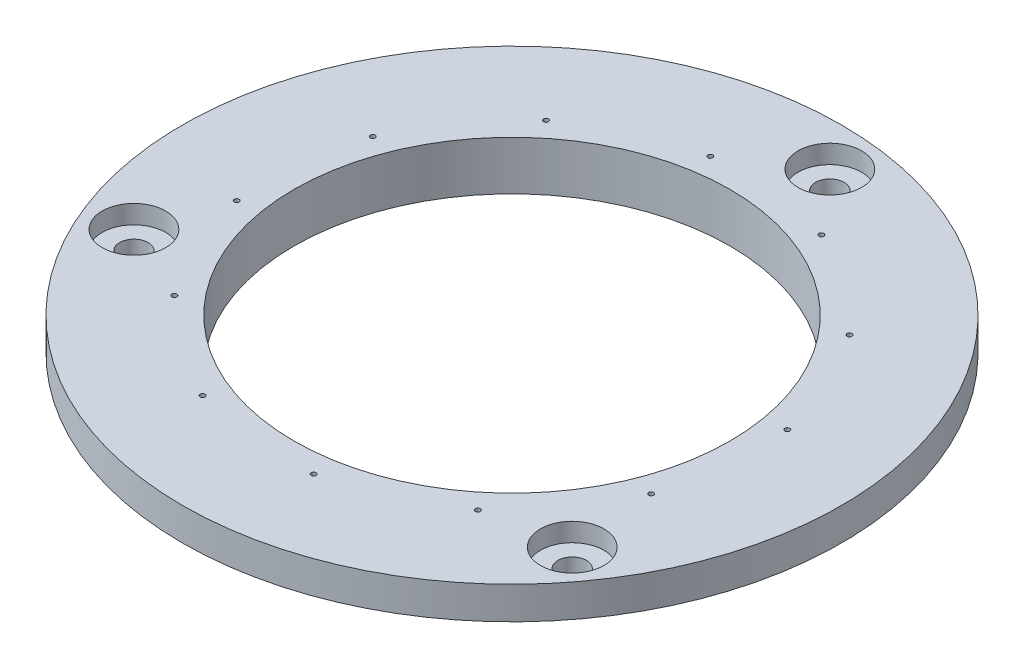
SolidWorks part; units mm, degrees
ref_plane "Front Plane" through (0, 0, 0) normal (0, 0, 1) x (1, 0, 0)
ref_plane "Top Plane" through (0, 0, 0) normal (0, 1, 0) x (1, 0, 0)
ref_plane "Right Plane" through (0, 0, 0) normal (1, 0, 0) x (0, 0, -1)
sketch "Sketch2" plane through (0, 0, 0) normal (0, 1, 0) x (1, 0, 0)
  circle A0 centre (0, 0) radius 63.5
  circle A1 centre (0, 0) radius 42
  dimension "D1" = 127
  dimension "D2" = 84
extrude "Boss-Extrude1" add sketch "Sketch2" along normal blind 9.45
sketch "Sketch15" plane through (0, 9.45, 0) normal (0, 1, 0) x (1, 0, 0)
  line L1 (6.244, 55) -> (-50.7534, -22.0925)
  line L2 (-50.7534, -22.0925) -> (44.5094, -32.9075)
  line L3 (44.5094, -32.9075) -> (6.244, 55)
  circle A0 centre (0, 0) radius 27.6766 construction
  point P1 (0, 53.3963)
  point P7 (0, 55.2781)
  point P8 (0, 56.4543)
  point P9 (0, 0)
  point P10 (0, 0)
  point P11 (0, 0)
  point P12 (0, 0)
  point P13 (0, 0)
  point P14 (0, 0)
  point P15 (0, 0)
  point P16 (0, 0)
  point P17 (0, 0)
  point P18 (0, 0)
  point P19 (0, 0)
  point P20 (0, 0)
hole_wizard "CBORE for M5 Hex Head Bolt1" positions "3DSketch8" profile "Sketch16" counterbore size "M5" standard "ANSI Metric"
sketch3d "3DSketch8"
  point P0 (6.244, 9.45, -55)
  point P3 (44.5094, 9.45, 32.9075)
  point P6 (-50.7534, 9.45, 22.0925)
sketch "Sketch16" plane through (6.244, 9.45, -55) normal (1, 0, 0) x (0, 0, 1)
  line L0 (0, 0) -> (0, 21.4024)
  line L1 (0, 21.4024) -> (2.75, 19.75)
  line L2 (2.75, 19.75) -> (2.75, 3.58)
  line L3 (2.75, 3.58) -> (6.12, 3.58)
  line L4 (6.12, 3.58) -> (6.12, 0)
  line L5 (6.12, 0) -> (0, 0)
  line L10 (0, 21.4024) -> (-2.75, 19.75) construction
  line L11 (0, -6.35) -> (0, 107.95) construction
  dimension "Hole Dia." = 5.5
  dimension "Hole Depth" = 19.75
  dimension "C'Bore Dia." = 12.24
  dimension "C'Bore Depth" = 3.58
  dimension "Drill Angle" = 118
sketch "Sketch26" plane through (0, 0, 0) normal (0, 1, 0) x (1, 0, 0)
  circle A0 centre (0, 0) radius 63.5
  dimension "D1" = 127
ref_axis "Axis1" through (0, 9.45, 0) along (0, -1, 0)
sketch "Sketch27" plane through (0, 0, 0) normal (0, 0, 1) x (1, 0, 0)
  line L0 (63.5, 0) -> (-63.5, 0) construction
  line L1 (63.5, 0) -> (58.5912, 0)
  line L2 (63.5, 0) -> (63.5, 3.175)
  line L3 (63.5, 3.175) -> (58.5912, 3.175)
  line L4 (58.5912, 0) -> (58.5912, 3.175)
  line L5 (69.85, 0) -> (-69.85, 0) construction
  line L6 (63.5, 0) -> (63.5, 9.45) construction
  line L7 (63.5, 0) -> (63.5, 9.45)
  line L8 (0, 9.45) -> (0, 0) construction
  line L9 (0, 0) -> (0, 15.4643) construction
  dimension "D1" = 117.1823
  dimension "D2" = 3.175
revolve "Cut-Revolve1" cut sketch "Sketch27" angle 360 about L9 region at (61.0456, 1.5875, 0)
hole_wizard "M1.2x0.25 Tapped Hole1" positions "Sketch28" profile "Sketch29" tap size "M1.2x0.25" standard "ANSI Metric" end condition through all
sketch "Sketch28" plane through (-17.102, 9.45, -64.2994) normal (0, 1, 0) x (0.108, 0, -0.9941)
  point P0 (-95.0061, 8.4911)
  point P3 (-74.3741, 20.6104)
  point P6 (-50.4466, 20.79)
  point P9 (-29.6349, 8.9817)
  point P12 (-17.5156, -11.6503)
  point P15 (-17.3361, -35.5778)
  point P18 (-29.1443, -56.3895)
  point P21 (-49.7764, -68.5087)
  point P24 (-73.7039, -68.6883)
  point P27 (-94.5155, -56.8801)
  point P30 (-106.6348, -36.248)
  point P33 (-106.8144, -12.3205)
sketch "Sketch29" plane through (-35.8084, 9.45, 29.2331) normal (1, 0, 0) x (0, 0, 1)
  line L0 (0, 0) -> (0, 9.45)
  line L1 (0, 9.45) -> (0.475, 9.45)
  line L2 (0.475, 9.45) -> (0.475, 0)
  line L3 (0.475, 0) -> (0, 0)
  line L4 (0, -6.35) -> (0, 107.95) construction
  dimension "Thru Tap Drill Dia." = 0.95
  dimension "Thru Tap Drill Depth" = 9.45
cosmetic thread "Hole Thread1" parameters "D2"=1.2
cosmetic thread "Hole Thread2" parameters "D2"=1.2
cosmetic thread "Hole Thread3" parameters "D2"=1.2
cosmetic thread "Hole Thread4" parameters "D2"=1.2
cosmetic thread "Hole Thread5" parameters "D2"=1.2
cosmetic thread "Hole Thread6" parameters "D2"=1.2
cosmetic thread "Hole Thread7" parameters "D2"=1.2
cosmetic thread "Hole Thread8" parameters "D2"=1.2
cosmetic thread "Hole Thread9" parameters "D2"=1.2
cosmetic thread "Hole Thread10" parameters "D2"=1.2
cosmetic thread "Hole Thread11" parameters "D2"=1.2
cosmetic thread "Hole Thread12" parameters "D2"=1.2
equation "\"ODia\"= 5in"
equation "\"IDiam\"= 84mm"
equation "\"Thick\"= 9.45mm"
equation "\"Lip\"= 3.29mm"
equation "\"D1@Boss-Extrude1\"=\"Thick\""
